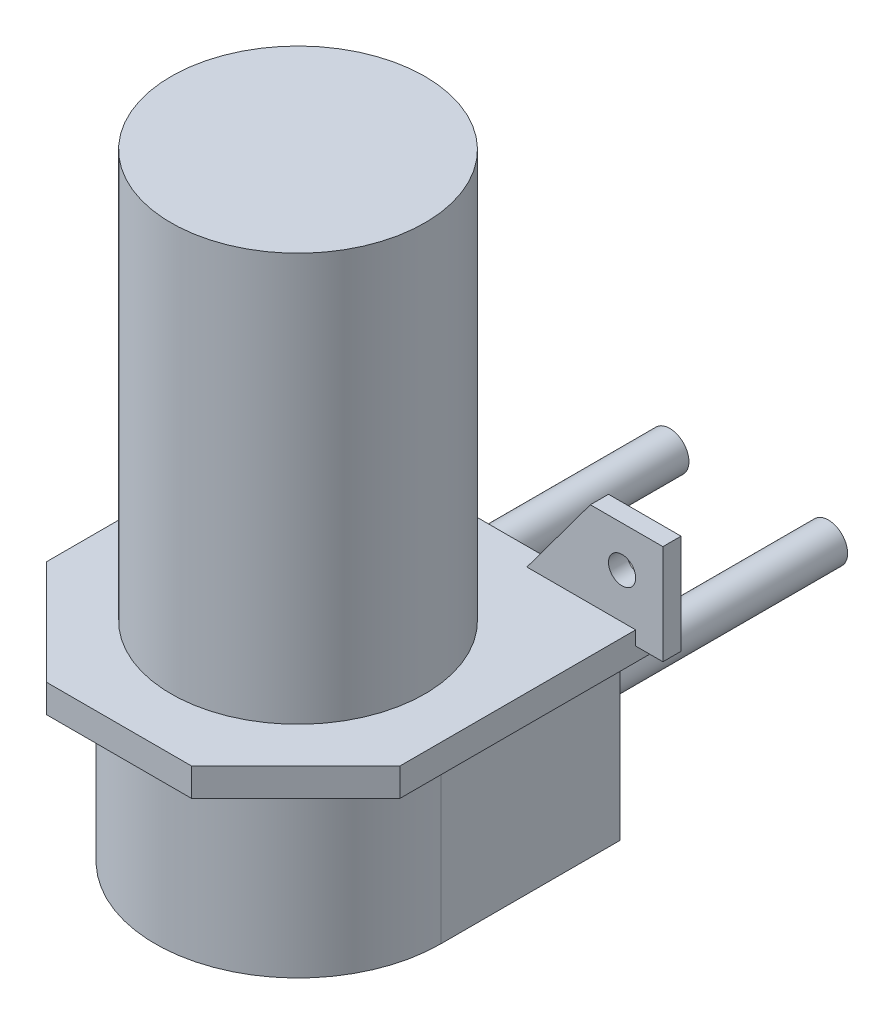
SolidWorks part; units mm, degrees
ref_plane "Front Plane" through (0, 0, 0) normal (0, 0, 1) x (1, 0, 0)
ref_plane "Top Plane" through (0, 0, 0) normal (0, 1, 0) x (1, 0, 0)
ref_plane "Right Plane" through (0, 0, 0) normal (1, 0, 0) x (0, 0, -1)
sketch "Sketch1" plane through (0, 0, 0) normal (0, 1, 0) x (1, 0, 0)
  circle A1 centre (0, 0) radius 14
  dimension "D1" = 28
extrude "Boss-Extrude1" add sketch "Sketch1" along normal blind 45
sketch "Sketch3" plane through (0, 0, 0) normal (0, -1, 0) x (1, 0, 0)
  line L0 (-8, 19.75) -> (-19.5, 8.25)
  line L1 (-8, 19.75) -> (8, 19.75)
  line L2 (-19.5, 8.25) -> (-19.5, -19.75)
  line L3 (-19.5, -19.75) -> (19.5, -19.75)
  line L4 (19.5, 8.25) -> (19.5, -19.75)
  line L5 (8, 19.75) -> (19.5, 8.25)
  line L6 (0, -1000) -> (0, 49000) construction
  line L7 (-1019.5, 8.25) -> (48980.5, 8.25) construction
  point P10 (0, 0)
  dimension "D1" = 39
  dimension "D2" = 19.5
  dimension "D3" = 39.5
  dimension "D4" = 19.75
  dimension "D5" = 8
  dimension "D6" = 16
  dimension "D7" = 28
extrude "Boss-Extrude3" add sketch "Sketch3" along normal blind 3.1
sketch "Sketch4" plane through (0, 0, 0) normal (0, 1, 0) x (1, 0, 0)
  line L0 (15.75, 0) -> (-15.75, 0) construction
  line L1 (0, 15.75) -> (0, -15.75) construction
  circle A0 centre (0, 0) radius 15.75
  dimension "D1" = 31.5
extrude "Boss-Extrude4" add sketch "Sketch4" against normal blind 23
sketch "Sketch5" plane through (0, -3.1, 0) normal (0, -1, 0) x (1, 0, 0)
  line L0 (-19.5, -19.75) -> (19.5, -19.75) construction
  line L1 (15.75, 0) -> (-15.75, 0)
  line L2 (15.75, 0) -> (15.75, -19.75)
  line L3 (15.75, -19.75) -> (-15.75, -19.75)
  line L4 (-15.75, 0) -> (-15.75, -19.75)
  circle A0 centre (0, 0) radius 15.75 construction
  circle A1 centre (0, 0) radius 15.75 construction
extrude "Boss-Extrude5" add sketch "Sketch5" along normal up to surface (19.9 mm away) up to face at (0, -23, 15.75)
sketch "Sketch6" plane through (0, 0, -19.75) normal (0, 0, -1) x (-1, 0, 0)
  line L0 (0, 0) -> (0, -23) construction
  line L1 (19.5, 0) -> (-19.5, 0) construction
  line L2 (15.75, -23) -> (-15.75, -23) construction
  circle A0 centre (-8.75, -13) radius 2.125
  circle A1 centre (8.75, -13) radius 2.125
  dimension "D3" = 4.25
  dimension "D4" = 4.25
  dimension "D1" = 17.5
  dimension "D2" = 8.75
  dimension "D5" = 10
  dimension "D6" = 10
extrude "Cut-Extrude1" cut sketch "Sketch6" against normal blind 19.6
sketch "Sketch7" plane through (0, 0, -19.75) normal (0, 0, -1) x (-1, 0, 0)
  line L0 (-19.5, -3.1) -> (-19.5, 0) construction
  line L1 (-19.5, -1.55) -> (-22.5, -1.55)
  line L2 (-19.5, -1.55) -> (-19.5, 0)
  line L3 (-18, 9.45) -> (-22.5, 9.45)
  line L4 (-22.5, -1.55) -> (-22.5, 9.45)
  line L5 (0, -1000) -> (0, 49000) construction
  line L6 (-18, 4.95) -> (-18, 9.45) construction
  line L7 (-18, 9.45) -> (-14.5, 9.45)
  line L8 (19.5, 0) -> (-19.5, 0) construction
  line L9 (19.5, 0) -> (-19.5, 0)
  line L10 (-14.5, 9.45) -> (-7.5, 0)
  line L11 (-18, 4.95) -> (-22.5, 4.95) construction
  line L12 (22.5, -1.55) -> (22.5, 9.45)
  line L13 (18, 9.45) -> (22.5, 9.45)
  line L14 (18, 9.45) -> (14.5, 9.45)
  line L15 (14.5, 9.45) -> (7.5, 0)
  line L16 (19.5, -1.55) -> (19.5, 0)
  line L17 (19.5, -1.55) -> (22.5, -1.55)
  circle A0 centre (-18, 4.95) radius 1.5
  circle A1 centre (18, 4.95) radius 1.5
  point P15 (0, 0)
  line M15 (19.5, 0) -> (-19.5, 0)
  line M16 (-19.5, 0) -> (-19.5, -3.1)
  line M22 (19.5, -3.1) -> (19.5, 0)
  dimension "D7" = 3
  dimension "D1" = 3
  dimension "D2" = 11
  dimension "D3" = 8
  dimension "D4" = 15
  dimension "D5" = 4.5
  dimension "D6" = 4.5
extrude "Boss-Extrude6" add sketch "Sketch7" against normal blind 2 contours L10 L7 L3 L4 L1 L9 A0 M16 | L17 L12 L13 L14 L15 A1 M22 M15 region at (-16.6713, 3.9791, -19.75) region at (16.6713, 3.9791, -19.75)
extrude "Boss-Extrude7" add sketch "Sketch6<2>" along normal blind 30 separate body
sketch "Sketch6<2>" plane through (0, 0, -19.75) normal (0, 0, -1) x (-1, 0, 0) same geometry as "Sketch6"
